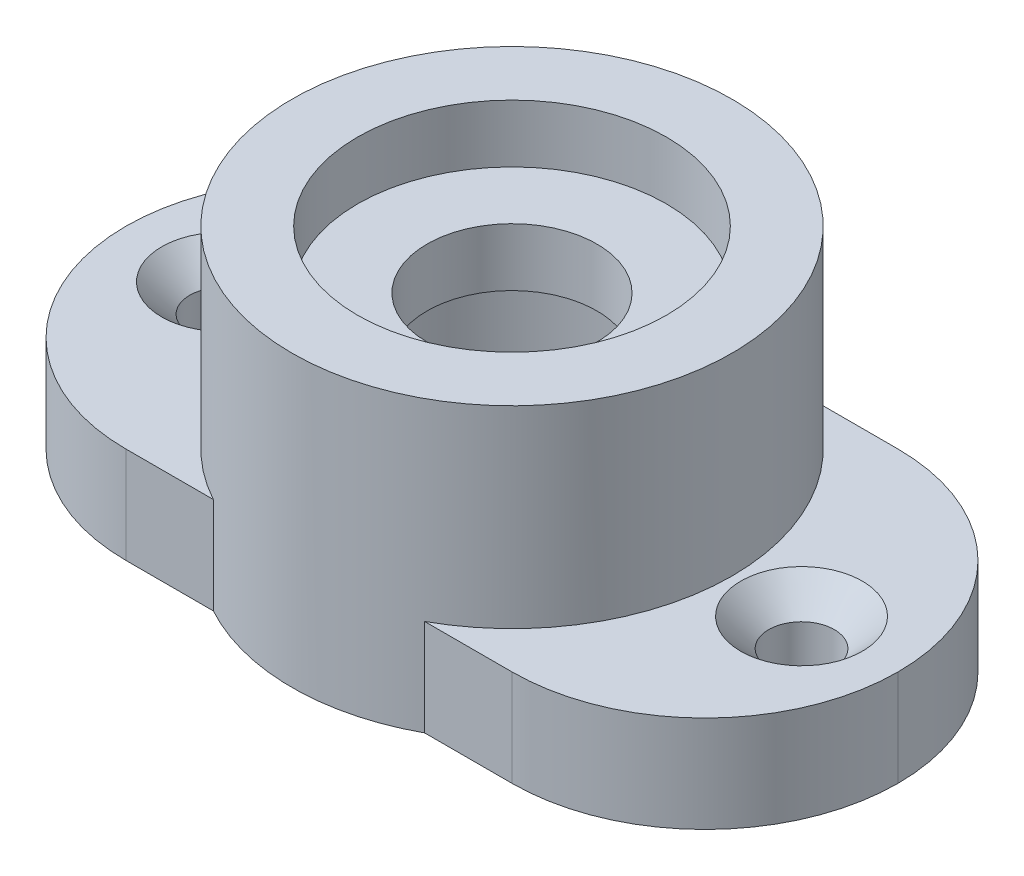
SolidWorks part; units mm, degrees
material "ABS PC"
ref_plane "Front Plane" through (0, 0, 0) normal (0, 0, 1) x (1, 0, 0)
ref_plane "Top Plane" through (0, 0, 0) normal (0, 1, 0) x (1, 0, 0)
ref_plane "Right Plane" through (0, 0, 0) normal (1, 0, 0) x (0, 0, -1)
sketch "Sketch1" plane through (0, 0, 0) normal (0, 1, 0) x (1, 0, 0)
  line L1 (-20, -10) -> (20, -10)
  line L2 (-20, -10) -> (-20, 10)
  line L3 (-20, 10) -> (20, 10)
  line L4 (20, -10) -> (20, 10)
  line L5 (-20, -10) -> (20, 10) construction
  line L6 (-20, 10) -> (20, -10) construction
  point P0 (0, 0)
  dimension "D1" = 40
  dimension "D2" = 20
extrude "Boss-Extrude1" add sketch "Sketch1" along normal blind 5
hole_wizard "CSK for M3 Flat Head Machine Screw1" positions "Sketch2" profile "Sketch3" countersink size "M3" standard "ANSI Metric" end condition through all
sketch "Sketch2" plane through (0, 5, 0) normal (0, 1, 0) x (1, 0, 0)
  line L0 (0, 0) -> (-15, 0) construction
  line L1 (0, 10) -> (0, -10) construction
  line L2 (20, 10) -> (-20, 10) construction
  line L3 (-20, -10) -> (20, -10) construction
  point P1 (-15, 0)
  point P14 (15, 0)
  dimension "D1" = 30
sketch "Sketch3" plane through (15, 5, 0) normal (1, 0, 0) x (0, 0, 1)
  line L0 (0, 0) -> (0, 5)
  line L1 (0, 5) -> (1.7, 5)
  line L2 (1.7, 5) -> (1.7, 1.45)
  line L3 (1.7, 1.45) -> (3.15, 0)
  line L5 (3.15, 0) -> (0, 0)
  line L6 (-1.7, 1.45) -> (-3.15, 0) construction
  line L11 (0, -6.35) -> (0, 107.95) construction
  dimension "Thru Hole Dia." = 3.4
  dimension "Thru Hole Depth" = 5
  dimension "Near C'Sink Dia." = 6.3
  dimension "Near C'Sink Angle" = 90
sketch "Sketch4" plane through (0, 5, 0) normal (0, 1, 0) x (1, 0, 0)
  circle A0 centre (0, 0) radius 4.4
  dimension "D1" = 8.8
extrude "Cut-Extrude1" cut sketch "Sketch4" against normal blind 5
sketch "Sketch5" plane through (0, 5, 0) normal (0, 1, 0) x (1, 0, 0)
  circle A2 centre (0, 0) radius 11.4
  circle A3 centre (0, 0) radius 11.4
  circle A5 centre (0, 0) radius 4.4
  circle A6 centre (0, 0) radius 4.4
  dimension "D1" = 7
  dimension "D2" = 0
extrude "Boss-Extrude2" add sketch "Sketch5" along normal blind 10
fillet "Fillet1" radius 10 4 edges at (20, 2.5, 10) (-20, 2.5, -10) (20, 2.5, -10) (-20, 2.5, 10)
sketch "Sketch6" plane through (0, 15, 0) normal (0, 1, 0) x (1, 0, 0)
  circle A1 centre (0, 0) radius 8
  circle A2 centre (0, 0) radius 4.4
  circle A3 centre (0, 0) radius 4.4
  dimension "D2" = 16
  dimension "D1" = 0
extrude "Cut-Extrude2" cut sketch "Sketch6" against normal blind 3
sketch "Sketch7" plane through (0, 0, 0) normal (0, -1, 0) x (1, 0, 0)
  circle A0 centre (0, 0) radius 8
  dimension "D1" = 16
extrude "Cut-Extrude3" cut sketch "Sketch7" against normal offset from surface (9 mm away) 3 up to face at (0, 12, 4.4)
sketch "Sketch8" plane through (0, 0, 0) normal (0, -1, 0) x (1, 0, 0)
  line L0 (-10, 10) -> (10, 10) construction
  line L1 (-5.4736, 10) -> (5.4736, 10)
  line L2 (-2.707, 0) -> (2.0774, 0) construction
  line L3 (-5.4736, -10) -> (5.4736, -10)
  arc A0 (-5.4736, 10) -> (5.4736, 10) centre (0, 0) cw
  arc A1 (5.4736, 10) -> (-5.4736, 10) centre (0, 0) ccw construction
  arc A2 (-5.4736, -10) -> (5.4736, -10) centre (0, 0) ccw
extrude "Boss-Extrude3" add sketch "Sketch8" against normal up to surface (5 mm away) up to face at (0, 5, 10.7)
